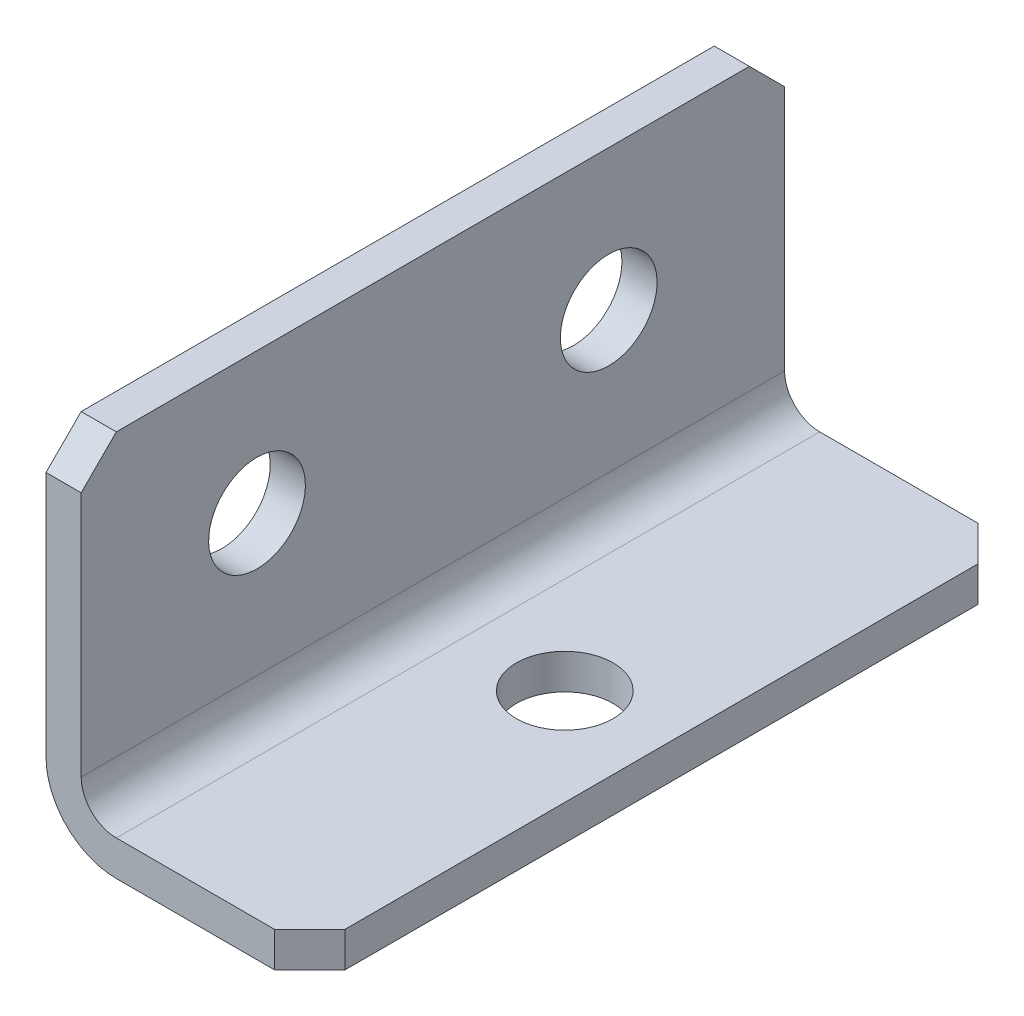
SolidWorks part; units mm, degrees
ref_plane "Front Plane" through (0, 0, 0) normal (0, 0, 1) x (1, 0, 0)
ref_plane "Top Plane" through (0, 0, 0) normal (0, 1, 0) x (1, 0, 0)
ref_plane "Right Plane" through (0, 0, 0) normal (1, 0, 0) x (0, 0, -1)
sketch "Sketch1" plane through (0, 0, 0) normal (0, 0, 1) x (1, 0, 0)
  line L0 (0, 4) -> (0, 20)
  line L1 (0, 20) -> (2, 20)
  line L2 (2, 20) -> (2, 4)
  line L3 (4, 2) -> (15, 2)
  line L4 (15, 2) -> (15, 0)
  line L5 (15, 0) -> (4, 0)
  arc A0 (2, 4) -> (4, 2) centre (4, 4) ccw
  arc A1 (0, 4) -> (4, 0) centre (4, 4) ccw
  point P11 (0, 0)
  dimension "D5" = 2
  dimension "D6" = 4
  dimension "D1" = 15
  dimension "D2" = 20
  dimension "D3" = 2
  dimension "D4" = 2
extrude "Boss-Extrude1" add sketch "Sketch1" along normal mid plane 40
sketch "Sketch2" plane through (2, 0, 0) normal (1, 0, 0) x (0, 0, -1)
  line L1 (0, 0) -> (0, 20) construction
  line L2 (-20, 20) -> (20, 20) construction
  circle A0 centre (-10, 12) radius 2.75
  circle A2 centre (10, 12) radius 2.75
  dimension "D1" = 5.5
  dimension "D2" = 10
  dimension "D3" = 8
extrude "Cut-Extrude1" cut sketch "Sketch2" against normal through all
sketch "Sketch3" plane through (0, 2, 0) normal (0, 1, 0) x (1, 0, 0)
  line L2 (15, -20) -> (4, -20) construction
  circle A0 centre (9.5, 0) radius 2.75
  point P0 (9.5, 0)
  point P9 (9.5, -20)
  dimension "D2" = 5.5
extrude "Cut-Extrude2" cut sketch "Sketch3" against normal through all
chamfer "Chamfer1" distance 2 angle 45 4 edges at (1, 20, -20) (15, 1, -20) (15, 1, 20) (1, 20, 20)
